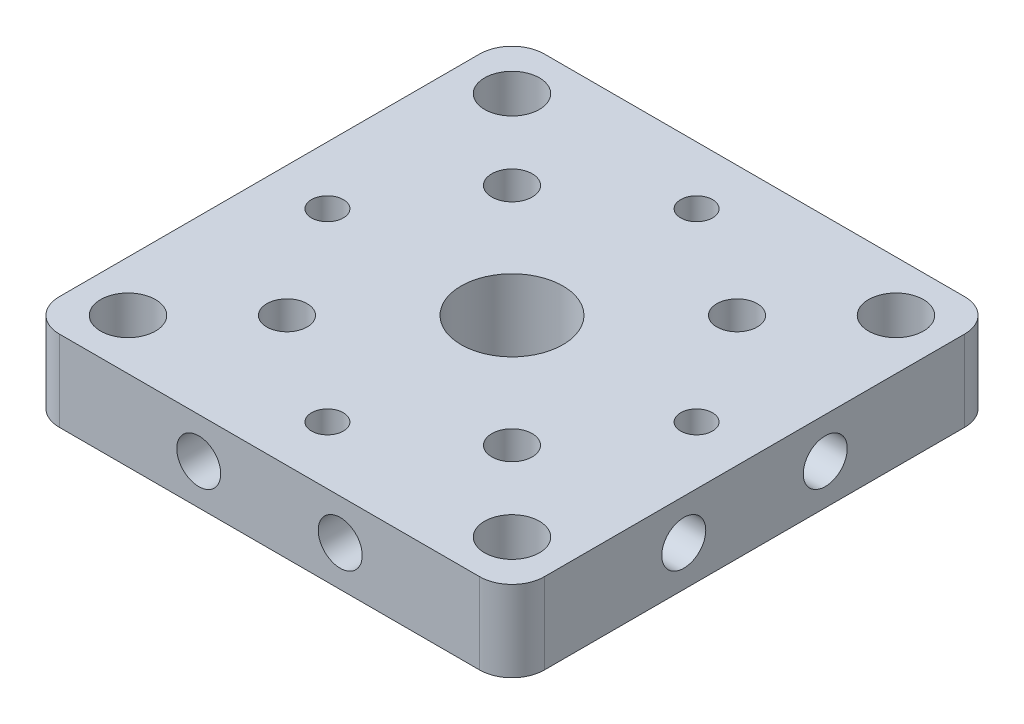
SolidWorks part; units mm, degrees
material "Alum Plate"
ref_plane "Front Plane" through (0, 0, 0) normal (0, 0, 1) x (1, 0, 0)
ref_plane "Top Plane" through (0, 0, 0) normal (0, 1, 0) x (1, 0, 0)
ref_plane "Right Plane" through (0, 0, 0) normal (1, 0, 0) x (0, 0, -1)
other "Bounding Box"
ref_plane "Default Plane" through (-8.9266, -12.7485, 0) normal (-0.1736, 0.9848, 0) x (0.9848, 0.1736, 0)
sketch "Sketch1" plane through (0, 0, 0) normal (0, 1, 0) x (1, 0, 0)
  line L0 (0, -12.5) -> (0, 12.5) construction
  line L1 (-14.5, 0) -> (0, 14.5) construction
  line L2 (-19.05, 19.05) -> (19.05, 19.05)
  line L3 (-19.05, 19.05) -> (-19.05, -19.05)
  line L4 (-19.05, -19.05) -> (19.05, -19.05)
  line L5 (19.05, 19.05) -> (19.05, -19.05)
  line L6 (-19.05, 19.05) -> (19.05, -19.05) construction
  line L7 (-19.05, -19.05) -> (19.05, 19.05) construction
  line L8 (8.8388, 8.8388) -> (-8.8388, 8.8388) construction
  line L9 (8.8388, 8.8388) -> (8.8388, -8.8388) construction
  line L10 (8.8388, -8.8388) -> (-8.8388, -8.8388) construction
  line L11 (-8.8388, 8.8388) -> (-8.8388, -8.8388) construction
  line L12 (8.8388, 8.8388) -> (-8.8388, -8.8388) construction
  line L13 (8.8388, -8.8388) -> (-8.8388, 8.8388) construction
  line L14 (-14.5, 0) -> (0, -14.5) construction
  line L15 (0, 14.5) -> (14.5, 0) construction
  line L16 (0, -14.5) -> (14.5, 0) construction
  line L17 (-14.5, 0) -> (14.5, 0) construction
  line L18 (0, 14.5) -> (0, -14.5) construction
  circle A0 centre (-15.24, 15.24) radius 1.3843 construction
  circle A1 centre (15.24, 15.24) radius 1.3843 construction
  circle A2 centre (15.24, -15.24) radius 1.3843 construction
  circle A3 centre (-15.24, -15.24) radius 1.3843 construction
  circle A4 centre (0, 0) radius 4
  circle A5 centre (8.8388, 8.8388) radius 1.5875
  circle A6 centre (8.8388, -8.8388) radius 1.5875
  circle A7 centre (-8.8388, -8.8388) radius 1.5875
  circle A8 centre (-8.8388, 8.8388) radius 1.5875
  circle A9 centre (-14.5, 0) radius 1.25
  circle A10 centre (0, 14.5) radius 1.25
  circle A11 centre (14.5, 0) radius 1.25
  circle A12 centre (0, -14.5) radius 1.25
  point P3 (0, 0)
  circle B0 centre (-9.8995, -9.8995) radius 1.2645 construction
  circle B1 centre (0, -8) radius 1.5875 construction
  circle B2 centre (0, 0) radius 4 construction
  circle B3 centre (9.8995, 9.8995) radius 1.2645 construction
  circle B4 centre (0, 8) radius 1.5875 construction
  circle B5 centre (9.8995, -9.8995) radius 1.2645 construction
  circle B6 centre (0, -12.5) radius 1.5875 construction
  circle B7 centre (-9.5, 0) radius 1.5875 construction
  circle B8 centre (-15.24, 15.24) radius 1.3843 construction
  circle B9 centre (15.24, 15.24) radius 1.3843 construction
  circle B10 centre (15.24, -15.24) radius 1.3843 construction
  circle B11 centre (-15.24, -15.24) radius 1.3843 construction
  circle B12 centre (9.5, 0) radius 1.5875 construction
  circle B13 centre (-9.8995, 9.8995) radius 1.2645 construction
  circle B14 centre (0, 12.5) radius 1.5875 construction
  dimension "D2" = 3.175
  dimension "D4" = 2.5
  dimension "D1" = 38.1
  dimension "D3" = 25
  dimension "D5" = 29
sketch_block_instance "Block-36mm gearbox motor block holes-1"
sketch_block "Block-36mm gearbox motor block holes"
extrude "Boss-Extrude1" add sketch "Sketch1" along normal mid plane 6.35 contours L5 L2 L3 L4 A12 A11 A9 A8 A10 A7 A6 A5 A4 A3 A2 A1 A0 region at (0, 0, -18.5112)
sketch "Sketch4" plane through (0, 0, 19.05) normal (0, 0, 1) x (1, 0, 0)
  line L0 (-5.5562, 0) -> (0, 0) construction
  line L1 (0, 0) -> (5.5562, 0) construction
  circle A0 centre (-5.5562, 0) radius 1.7272
  circle A1 centre (5.5562, 0) radius 1.7272
  dimension "D2" = 3.4544
  dimension "D1" = 11.1125
extrude "Cut-Extrude2" cut sketch "Sketch4" against normal blind 9.525
sketch "Sketch7" plane through (0, -3.175, 0) normal (0, -1, 0) x (1, 0, 0)
  line L0 (-19.05, 15.0813) -> (-15.0813, 15.0813) construction
  line L1 (-19.05, -19.05) -> (-19.05, 19.05) construction
  line L2 (-15.0813, 15.0813) -> (-15.0813, 19.05) construction
  line L3 (-19.05, 19.05) -> (19.05, 19.05) construction
  line L4 (0, 0) -> (-15.0813, 15.0813) construction
  line L5 (0, 0) -> (15.0813, 15.0812) construction
  circle A0 centre (-15.0813, 15.0813) radius 2.1526
  circle A1 centre (15.0813, 15.0812) radius 2.1527
  circle A2 centre (15.0812, -15.0813) radius 2.1527
  circle A3 centre (-15.0813, -15.0812) radius 2.1526
  dimension "D2" = 4.3053
  dimension "D1" = 3.9688
  dimension "D4" = 90
  dimension "D3" = 4
extrude "Cut-Extrude3" cut sketch "Sketch7" against normal through all
pattern_circular "CirPattern1" count 4 over 360 about axis through (0, 3.175, 0) along (0, -1, 0) of "Cut-Extrude2"
ref_plane "Plane1" through (0, -33.3502, 0) normal (0, -1, 0) x (-1, 0, 0)
sketch "Sketch6" plane through (0, -33.3502, 0) normal (0, -1, 0) x (-1, 0, 0)
  line L0 (19.05, 19.05) -> (-19.05, 19.05) construction
  line L1 (19.05, 19.05) -> (19.05, -19.05) construction
  line L2 (19.05, -19.05) -> (-19.05, -19.05) construction
  line L3 (-19.05, 19.05) -> (-19.05, -19.05) construction
  line L12 (19.05, 19.05) -> (-19.05, 19.05)
  line L13 (19.05, 19.05) -> (19.05, -19.05)
  line L14 (19.05, -19.05) -> (-19.05, -19.05)
  line L15 (-19.05, 19.05) -> (-19.05, -19.05)
  circle A8 centre (0, 0) radius 6.5
  circle A17 centre (-15.0812, 15.0813) radius 2.1526
  circle A18 centre (15.0813, 15.0812) radius 2.1526
  circle A19 centre (15.0813, -15.0813) radius 2.1527
  circle A20 centre (-15.0813, -15.0812) radius 2.1526
  circle A21 centre (-15.0812, 15.0813) radius 2.1527 construction
  dimension "D2" = 13
extrude "Boss-Extrude2" add sketch "Sketch6" along normal blind 3.175 separate body
fillet "Fillet1" radius 2.54 4 edges at (-19.05, 0, 19.05) (-19.05, 0, -19.05) (19.05, 0, -19.05) (19.05, 0, 19.05)
fillet "Fillet2" radius 2.54 4 edges at (-19.05, -34.9377, 19.05) (-19.05, -34.9377, -19.05) (19.05, -34.9377, -19.05) (19.05, -34.9377, 19.05)
delete or keep bodies "Body-Delete/Keep 1" [suppressed] type keep bodies bodies 108
delete or keep bodies "Body-Delete/Keep 2" type keep bodies bodies 107
